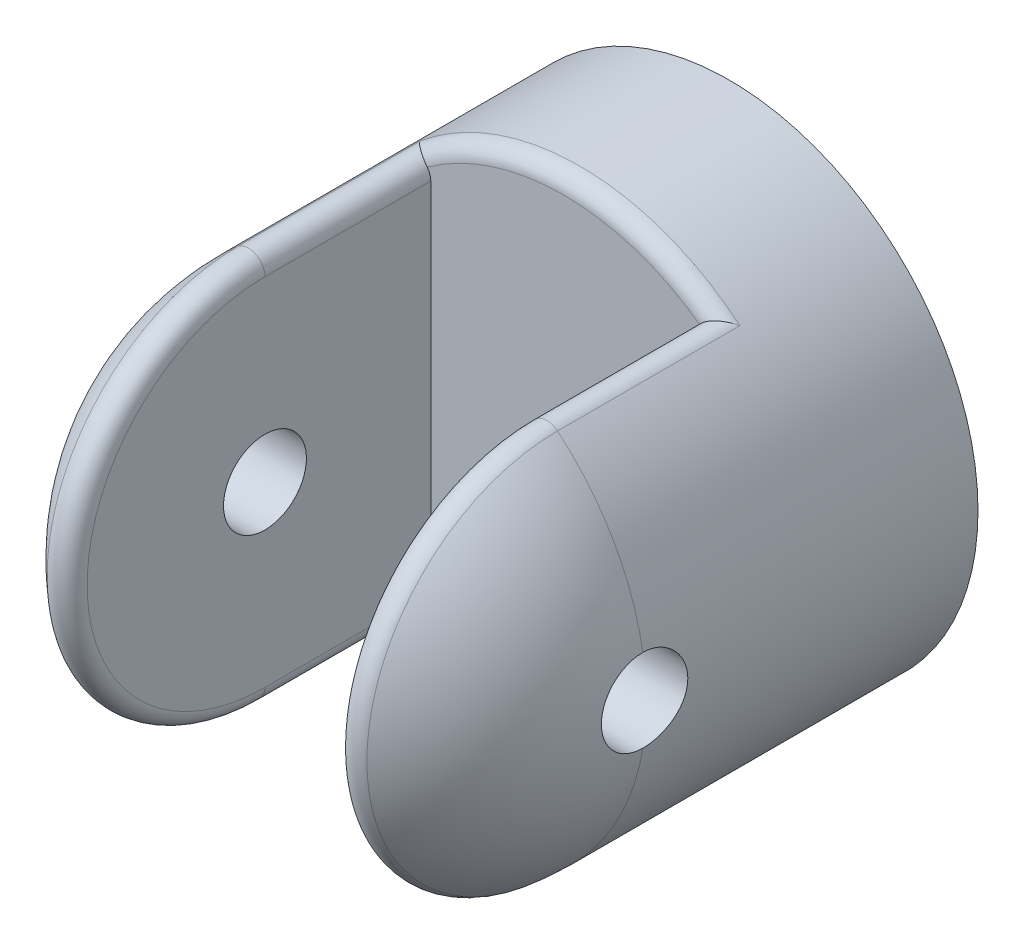
SolidWorks part; units mm, degrees
ref_plane "Alzado" through (0, 0, 0) normal (0, 0, 1) x (1, 0, 0)
ref_plane "Planta" through (0, 0, 0) normal (0, 1, 0) x (1, 0, 0)
ref_plane "Vista lateral" through (0, 0, 0) normal (1, 0, 0) x (0, 0, -1)
sketch "Croquis1" plane through (0, 0, 0) normal (0, 0, 1) x (1, 0, 0)
  circle A0 centre (0, 0) radius 7.5
  dimension "D1" = 15
extrude "Saliente-Extruir1" add sketch "Croquis1" along normal blind 10
dome "Cúpula1" faces to dome 1 distance 7.5 reverse direction no elliptical dome no face at (7.5, 0, 10) parameters "D1"=7.5
sketch "Croquis2" plane through (0, 0, 0) normal (0, 1, 0) x (1, 0, 0)
  line L0 (7.5, -10) -> (-7.5, -10) construction
  line L2 (-4, -10) -> (-4, -17.5)
  line L3 (-4, -17.5) -> (4, -17.5)
  line L4 (4, -9.5) -> (4, -17.5)
  line L5 (7.5, 0) -> (-7.5, 0) construction
  line L6 (0, 0) -> (0, -17.5) construction
  line L8 (-4, -10) -> (-4, -5)
  line L9 (-4, -5) -> (4, -5)
  line L10 (4, -9.5) -> (4, -5)
  arc A0 (-7.5, -10) -> (7.5, -10) centre (0, -10) ccw construction
  dimension "D1" = 8
  dimension "D2" = 8
  dimension "D3" = 4.5
  dimension "D4" = 5
extrude "Cortar-Extruir1" cut sketch "Croquis2" along normal blind 10 and the other way blind 19
sketch "Croquis3" plane through (0, 0, 0) normal (1, 0, 0) x (0, 0, -1)
  line L0 (-10, -6.3443) -> (-10, 6.3443) construction
  circle A0 centre (-10, 0) radius 1.25
  dimension "D1" = 2.5
extrude "Cortar-Extruir2" cut sketch "Croquis3" along normal blind 11 and the other way blind 19
fillet "Redondeo1" radius 0.5 8 edges at (4, -6.3443, 7.5) (4, 6.3443, 7.5) (-4, -6.3443, 7.5) (-4, 0, 16.3443) (0, -7.5, 5) (0, 7.5, 5) (4, 0, 16.3443) (-4, 6.3443, 7.5)
